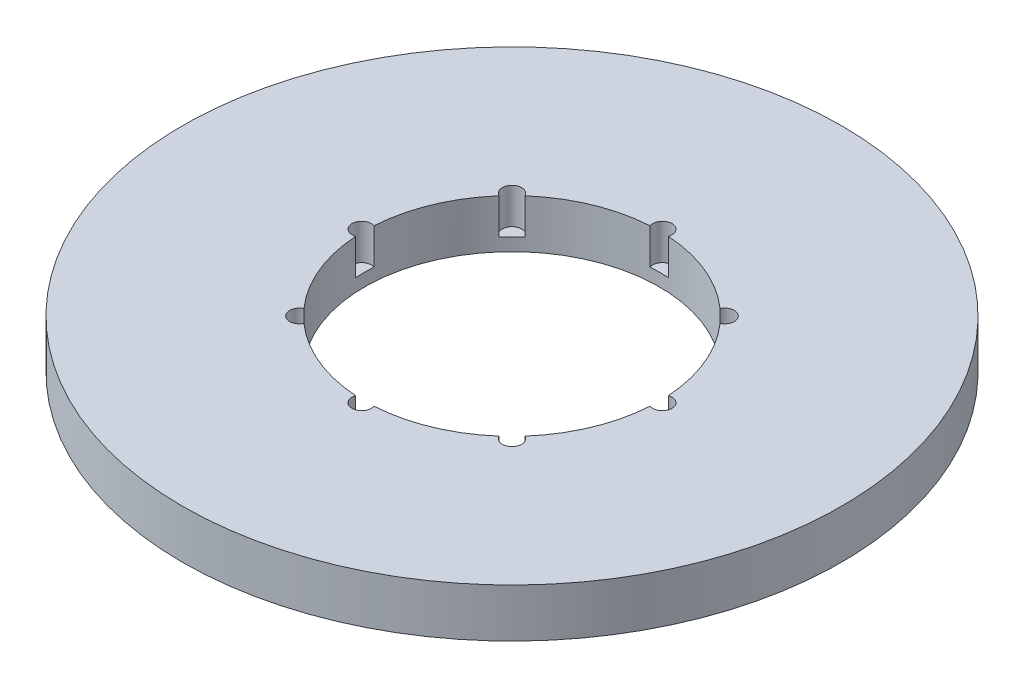
SolidWorks part; units mm, degrees
ref_plane "Front Plane" through (0, 0, 0) normal (0, 0, 1) x (1, 0, 0)
ref_plane "Top Plane" through (0, 0, 0) normal (0, 1, 0) x (1, 0, 0)
ref_plane "Right Plane" through (0, 0, 0) normal (1, 0, 0) x (0, 0, -1)
sketch "Sketch1" plane through (0, 0, 0) normal (0, 1, 0) x (1, 0, 0)
  circle A0 centre (0, 0) radius 95
  dimension "FLANGE_OD" = 190
extrude "Boss-Extrude1" add sketch "Sketch1" along normal blind 14
sketch "Sketch2" plane through (0, 0, 0) normal (0, 1, 0) x (1, 0, 0)
  circle A0 centre (0, 0) radius 42.5
  dimension "BORE_D" = 85
extrude "Cut-Extrude1" cut sketch "Sketch2" along normal through all
sketch "Sketch3" plane through (0, 14, 0) normal (0, 1, 0) x (1, 0, 0)
  circle A0 centre (0, 0) radius 43.3472 construction
  circle A1 centre (-43.3472, 0) radius 2.7841
  dimension "BOLT_D" = 5.5683
  dimension "BOLT_PCD" = 86.6944
extrude "Cut-Extrude2" cut sketch "Sketch3" against normal blind 10.3246
pattern_circular "CirPattern1" count 8 over 360 about axis through (0, 0, 0) along (0, 1, 0) of "Cut-Extrude2"
